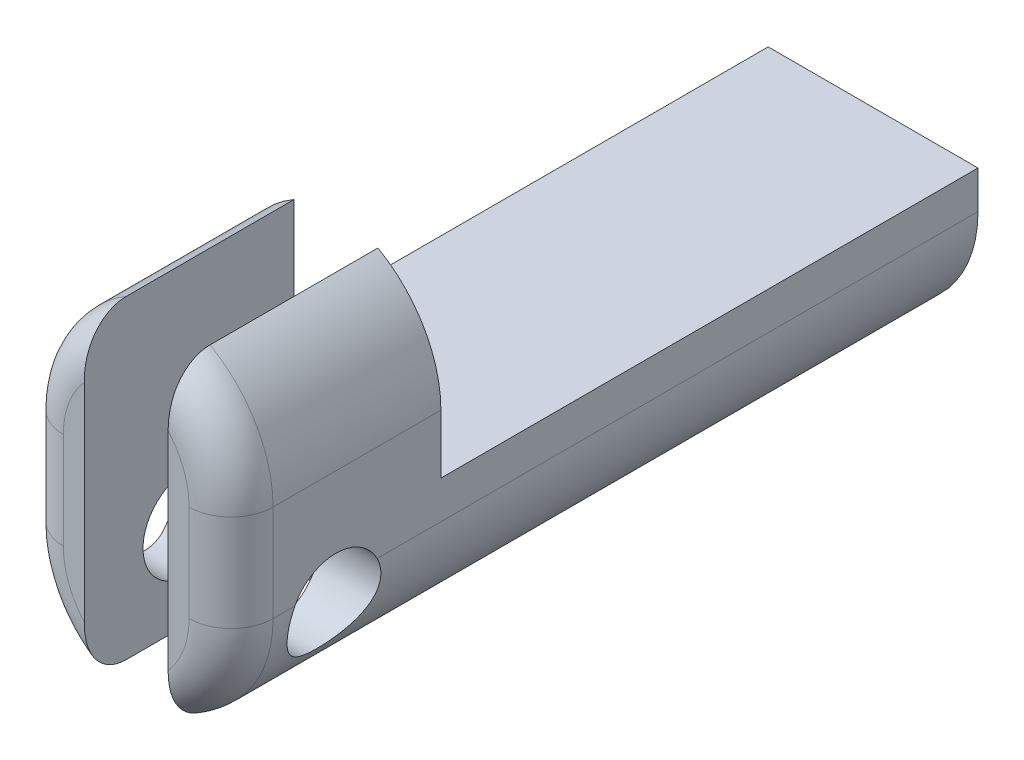
SolidWorks part; units mm, degrees
ref_plane "前视基准面" through (0, 0, 0) normal (0, 0, 1) x (1, 0, 0)
ref_plane "上视基准面" through (0, 0, 0) normal (0, 1, 0) x (1, 0, 0)
ref_plane "右视基准面" through (0, 0, 0) normal (1, 0, 0) x (0, 0, -1)
other "Configuration Table"
sketch "草图1" plane through (0, 0, 0) normal (0, 0, 1) x (1, 0, 0)
  line L0 (2.5, 1.95) -> (-2.5, 1.95)
  line L1 (-2.5, 1.95) -> (-2.5, -1.95)
  line L2 (-2.5, -1.95) -> (2.5, -1.95)
  line L3 (2.5, -1.95) -> (2.5, 1.95)
extrude "凸台-拉伸1" add sketch "草图1" along normal blind 12.8
sketch "草图2" plane through (0, 0, 0) normal (0, 0, -1) x (-1, 0, 0)
  line L0 (2.5, 1.95) -> (2.5, -1.95) construction
  line L1 (2.5, -1.95) -> (-2.5, -1.95) construction
  circle A0 centre (0, -0.05) radius 1
  dimension "D1" = 2.5
  dimension "D2" = 1.9
  dimension "D3" = 2
extrude "切除-拉伸1" cut sketch "草图2" against normal blind 5
sketch "草图3" plane through (0, 0, 12.8) normal (0, 0, 1) x (1, 0, 0)
  line L0 (2.5, 5.95) -> (1, 5.95)
  line L1 (1, 5.95) -> (1, -1.95)
  line L2 (1, -1.95) -> (2.5, -1.95)
  line L3 (2.5, -1.95) -> (2.5, 5.95)
  line L4 (-2.5, -1.95) -> (2.5, -1.95) construction
  line L5 (2.5, -1.95) -> (2.5, 1.95) construction
  line L6 (-1, 5.95) -> (-2.5, 5.95)
  line L7 (-2.5, 5.95) -> (-2.5, -1.95)
  line L8 (-2.5, -1.95) -> (-1, -1.95)
  line L9 (-1, -1.95) -> (-1, 5.95)
  line L10 (-2.5, 1.95) -> (-2.5, -1.95) construction
  dimension "D1" = 7.9
  dimension "D2" = 1.5
  dimension "D3" = 1.5
  dimension "D4" = 7.9
extrude "凸台-拉伸2" add sketch "草图3" along normal blind 5
sketch "草图4" plane through (2.5, 0, 0) normal (1, 0, 0) x (0, 0, -1)
  line L0 (-17.8, -1.95) -> (0, -1.95) construction
  line L1 (-17.8, -1.95) -> (-17.8, 5.95) construction
  circle A0 centre (-15.3, 0.55) radius 1.1
  dimension "D1" = 2.5
  dimension "D3" = 2.2
  dimension "D2" = 2.5
extrude "切除-拉伸2" cut sketch "草图4" against normal blind 5
fillet "圆角1" radius 3 2 edges at (-2.5, -1.95, 8.9) (2.5, -1.95, 8.9)
fillet "圆角2" radius 3 2 edges at (2.5, 5.95, 15.3) (-2.5, 5.95, 15.3)
fillet "圆角3" radius 1 6 edges at (-2.0981, -0.45, 17.8) (-2.5, 2.201, 17.8) (2.0981, -0.45, 17.8) (2.5, 2.201, 17.8) (-2.0981, 4.8519, 17.8) (2.0981, 4.8519, 17.8)
